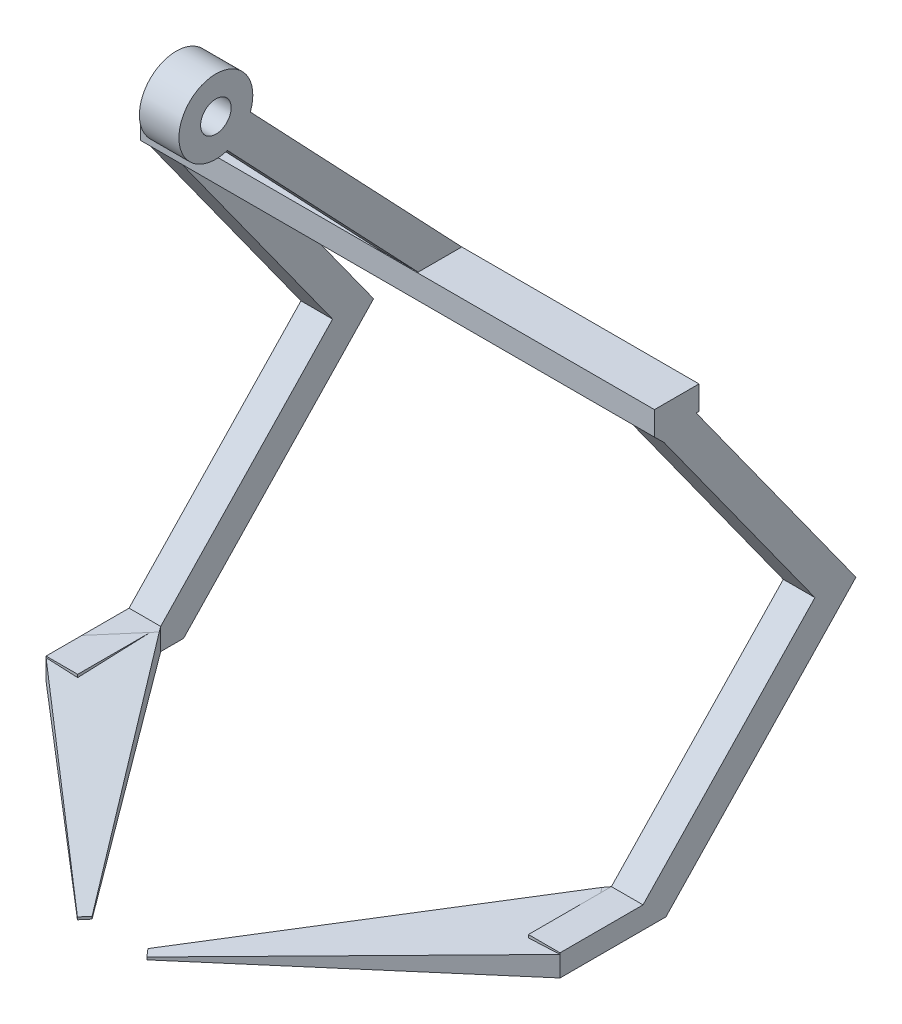
SolidWorks part; units mm, degrees
ref_plane "Front Plane" through (0, 0, 0) normal (0, 0, 1) x (1, 0, 0)
ref_plane "Top Plane" through (0, 0, 0) normal (0, 1, 0) x (1, 0, 0)
ref_plane "Right Plane" through (0, 0, 0) normal (1, 0, 0) x (0, 0, -1)
sketch "Sketch1" plane through (0, 0, 0) normal (1, 0, 0) x (0, 0, -1)
  line L0 (-48.3551, -11.0607) -> (-18.7049, -42.2714) construction
  line L1 (-46.8959, -15.5005) -> (-20.1549, -43.6489)
  line L2 (-43.9959, -12.7455) -> (-17.2549, -40.8939)
  line L3 (-46.9051, -9.6832) -> (-17.2549, -40.8939) construction
  line L4 (-49.8051, -12.4382) -> (-20.1549, -43.6489) construction
  line L5 (-17.2549, -40.8939) -> (-20.1549, -43.6489)
  arc A0 (-43.9959, -12.7455) -> (-46.8959, -15.5005) centre (-48.3551, -11.0607) ccw
  circle A1 centre (-48.3551, -11.0607) radius 1.933
  dimension "D1" = 2
  dimension "D2" = 2
extrude "Boss-Extrude2" add sketch "Sketch1" along normal blind 5
sketch "Sketch2" plane through (5, 0, 0) normal (1, 0, 0) x (0, 0, -1)
  line L1 (-17.2549, -40.8939) -> (-22.8861, -40.8939)
  line L2 (-17.2549, -40.8939) -> (-17.2549, -43.9088)
  line L3 (-17.2549, -43.9088) -> (-22.8861, -43.9088)
  line L4 (-22.8861, -40.8939) -> (-22.8861, -43.9088)
extrude "Boss-Extrude3" add sketch "Sketch2" along normal blind 30 and the other way blind 35
sketch "Sketch3" plane through (35, 0, 0) normal (1, 0, 0) x (0, 0, -1)
  line L0 (-20.0705, -43.9088) -> (0, -71.8095) construction
  line L1 (-22.8861, -43.9088) -> (-17.2549, -43.9088) construction
  line L2 (0, -71.8095) -> (-22.8861, -95.7939) construction
  line L3 (-21.6941, -45.0767) -> (-2.593, -71.6298)
  line L4 (-2.593, -71.6298) -> (-24.333, -94.4132)
  line L5 (-18.4469, -42.7409) -> (2.593, -71.9892)
  line L6 (2.593, -71.9892) -> (-21.4391, -97.1746)
  line L7 (-21.6941, -45.0767) -> (-22.8861, -43.9088)
  line L8 (-22.8861, -43.9088) -> (-18.4469, -42.7409)
  line L10 (-34.8288, -97.1746) -> (-21.4391, -97.1746)
  line L11 (-24.333, -94.4132) -> (-34.8288, -94.4132)
  line L12 (-34.8288, -94.4132) -> (-34.8288, -97.1746)
  dimension "D1" = 2
  dimension "D2" = 2
extrude "Boss-Extrude4" add sketch "Sketch3" against normal blind 4
pattern_linear "LPattern1" count 2 spacing 61 along (-1, 0, 0) of "Boss-Extrude4"
sketch "Sketch6" plane through (0, -94.4132, 0) normal (0, 1, 0) x (1, 0, 0)
  line L0 (2.5, -17.2549) -> (2.5, -62.7402) construction
  line L1 (5, -17.2549) -> (0, -17.2549) construction
  line L2 (6.8886, -58.9712) -> (35, -34.8288) construction
  line L3 (31, -24.333) -> (6.0346, -57.9769)
  line L4 (6.8886, -58.9712) -> (35, -34.8288)
  line L5 (35, -34.8288) -> (35, -24.333)
  line L6 (35, -24.333) -> (31, -24.333)
  line L11 (6.0346, -57.9769) -> (6.8886, -58.9712)
  line L12 (-1.8886, -58.9712) -> (-30, -34.8288) construction
  line L13 (-1.0346, -57.9769) -> (-1.8886, -58.9712)
  line L14 (-1.8886, -58.9712) -> (-30, -34.8288)
  line L15 (-26, -24.333) -> (-1.0346, -57.9769)
  line L16 (-30, -24.333) -> (-26, -24.333)
  line L17 (-30, -34.8288) -> (-30, -24.333)
  line M7 (31, -24.333) -> (31, -34.8288)
  line M8 (31, -34.8288) -> (35, -34.8288)
extrude "Boss-Extrude7" add sketch "Sketch6" against normal through all separate body contours L14 | L3 L4 M8 M7 region at (22.1769, -94.4132, 41.2405) region at (-19.0423, -94.4132, 39.2309)
chamfer "Chamfer4" distance 40 angle 3.5 1 edges at (-1.4616, -94.4132, 58.474) first distance on face at (-17.7846, -94.4132, 40.0886)
chamfer "Chamfer5" distance 40 angle 3.5 1 edges at (6.4616, -94.4132, 58.474) first distance on face at (21.9846, -94.4132, 42.1877)
